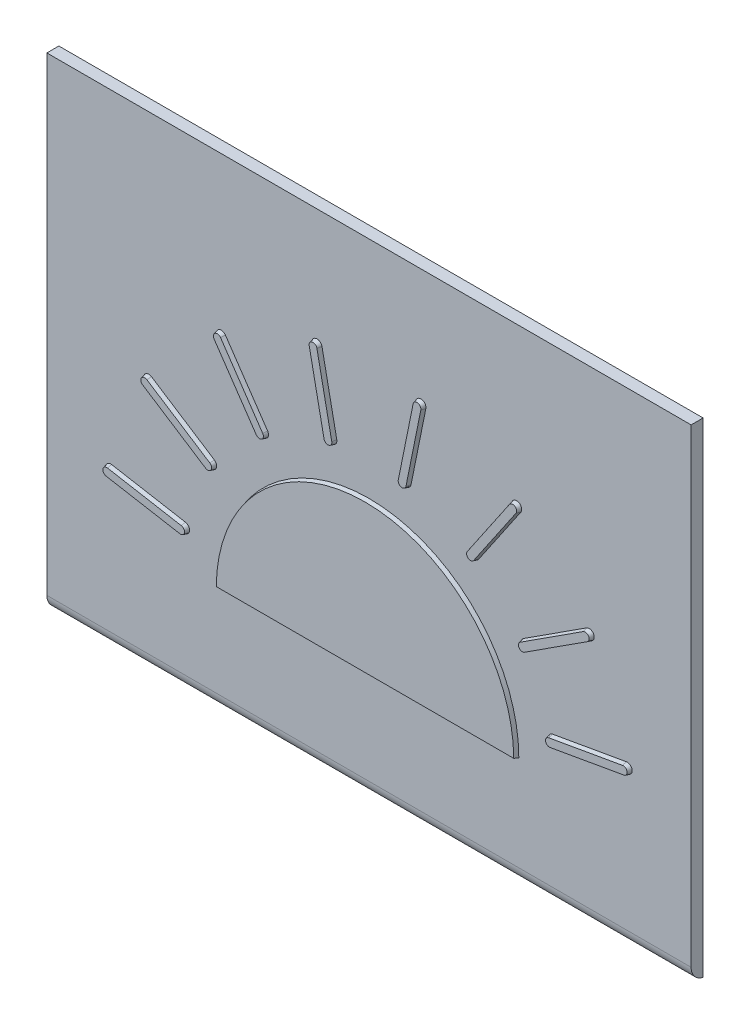
SolidWorks part; units mm, degrees
material "ABS"
ref_plane "Front Plane" through (0, 0, 0) normal (0, 0, 1) x (1, 0, 0)
ref_plane "Top Plane" through (0, 0, 0) normal (0, 1, 0) x (1, 0, 0)
ref_plane "Right Plane" through (0, 0, 0) normal (1, 0, 0) x (0, 0, -1)
sketch "Sketch1" plane through (0, 0, 0) normal (0, 0, 1) x (1, 0, 0)
  line L1 (0, 0) -> (129, 0)
  line L2 (0, 0) -> (0, 97)
  line L3 (0, 97) -> (129, 97)
  line L4 (129, 0) -> (129, 97)
  dimension "D1" = 97
  dimension "D2" = 129
extrude "Boss-Extrude1" add sketch "Sketch1" along normal blind 2.4
fillet "Fillet1" radius 3 1 edges at (64.5, 0, 2.4)
sketch "Sketch2" plane through (0, 0, 2.4) normal (0, 0, 1) x (1, 0, 0)
  line L0 (0, 22) -> (129, 22) construction
  line L1 (0, 97) -> (0, 2.9394) construction
  line L2 (129, 2.9394) -> (129, 97) construction
  line L3 (64.5, 22) -> (64.5, 97) construction
  line L4 (129, 97) -> (0, 97) construction
  line L5 (34.5, 22) -> (94.5, 22)
  line L6 (64.5, 22) -> (-4.5278, 34.1715) construction
  line L7 (12.7976, 31.1165) -> (27.5697, 28.5118) construction
  line L8 (12.9712, 32.1013) -> (27.7434, 29.4966)
  line L9 (12.6239, 30.1317) -> (27.3961, 27.527)
  line L10 (64.5, 22) -> (5.6203, 60.0285) construction
  line L11 (20.3986, 50.4837) -> (32.999, 42.3455) construction
  line L12 (20.9412, 51.3237) -> (33.5416, 43.1855)
  line L13 (19.8561, 49.6437) -> (32.4565, 41.5055)
  line L14 (64.5, 22) -> (25.0154, 79.9133) construction
  line L15 (34.9257, 65.3775) -> (43.3755, 52.984) construction
  line L16 (35.7519, 65.9409) -> (44.2017, 53.5473)
  line L17 (34.0995, 64.8142) -> (42.5493, 52.4206)
  line L18 (64.5, 22) -> (50.6114, 90.7029) construction
  line L19 (54.0973, 73.4591) -> (57.0695, 58.7565) construction
  line L20 (55.0775, 73.6572) -> (58.0497, 58.9546)
  line L21 (53.1172, 73.2609) -> (56.0893, 58.5583)
  line L22 (64.5, 22) -> (78.3886, 90.7029) construction
  line L23 (74.9027, 73.4591) -> (71.9305, 58.7565) construction
  line L24 (75.8828, 73.2609) -> (72.9107, 58.5583)
  line L25 (73.9225, 73.6572) -> (70.9503, 58.9546)
  line L26 (64.5, 22) -> (103.9846, 79.9133) construction
  line L27 (94.0743, 65.3775) -> (85.6245, 52.984) construction
  line L28 (94.9005, 64.8142) -> (86.4507, 52.4206)
  line L29 (93.2481, 65.9409) -> (84.7983, 53.5473)
  line L30 (64.5, 22) -> (123.3797, 60.0285) construction
  line L31 (108.6014, 50.4837) -> (96.001, 42.3455) construction
  line L32 (109.1439, 49.6437) -> (96.5435, 41.5055)
  line L33 (108.0588, 51.3237) -> (95.4584, 43.1855)
  line L34 (64.5, 22) -> (133.5278, 34.1715) construction
  line L35 (116.2024, 31.1165) -> (101.4303, 28.5118) construction
  line L36 (116.3761, 30.1317) -> (101.6039, 27.527)
  line L37 (116.0288, 32.1013) -> (101.2566, 29.4966)
  arc A0 (94.5, 22) -> (34.5, 22) centre (64.5, 22) ccw
  arc A1 (12.9712, 32.1013) -> (12.6239, 30.1317) centre (12.7976, 31.1165) ccw
  arc A2 (27.3961, 27.527) -> (27.7434, 29.4966) centre (27.5697, 28.5118) ccw
  arc A3 (20.9412, 51.3237) -> (19.8561, 49.6437) centre (20.3986, 50.4837) ccw
  arc A4 (32.4565, 41.5055) -> (33.5416, 43.1855) centre (32.999, 42.3455) ccw
  arc A5 (35.7519, 65.9409) -> (34.0995, 64.8142) centre (34.9257, 65.3775) ccw
  arc A6 (42.5493, 52.4206) -> (44.2017, 53.5473) centre (43.3755, 52.984) ccw
  arc A7 (55.0775, 73.6572) -> (53.1172, 73.2609) centre (54.0973, 73.4591) ccw
  arc A8 (56.0893, 58.5583) -> (58.0497, 58.9546) centre (57.0695, 58.7565) ccw
  arc A9 (75.8828, 73.2609) -> (73.9225, 73.6572) centre (74.9027, 73.4591) ccw
  arc A10 (70.9503, 58.9546) -> (72.9107, 58.5583) centre (71.9305, 58.7565) ccw
  arc A11 (94.9005, 64.8142) -> (93.2481, 65.9409) centre (94.0743, 65.3775) ccw
  arc A12 (84.7983, 53.5473) -> (86.4507, 52.4206) centre (85.6245, 52.984) ccw
  arc A13 (109.1439, 49.6437) -> (108.0588, 51.3237) centre (108.6014, 50.4837) ccw
  arc A14 (95.4584, 43.1855) -> (96.5435, 41.5055) centre (96.001, 42.3455) ccw
  arc A15 (116.3761, 30.1317) -> (116.0288, 32.1013) centre (116.2024, 31.1165) ccw
  arc A16 (101.2566, 29.4966) -> (101.6039, 27.527) centre (101.4303, 28.5118) ccw
  point P15 (20.1837, 29.8142)
  point P20 (64.5, 22)
  point P27 (26.6988, 46.4146)
  point P35 (39.1506, 59.1807)
  point P43 (55.5834, 66.1078)
  point P51 (73.4166, 66.1078)
  point P59 (89.8494, 59.1807)
  point P67 (102.3012, 46.4146)
  point P75 (108.8163, 29.8142)
  point P80 (64.5, 22)
  dimension "D2" = 30
  dimension "D5" = 1
  dimension "D1" = 75
  dimension "D4" = 10
  dimension "D3" = 15
  dimension "D6" = 45
  dimension "D7" = 8
extrude "Boss-Extrude2" add sketch "Sketch2" along normal blind 0.8 draft 15
